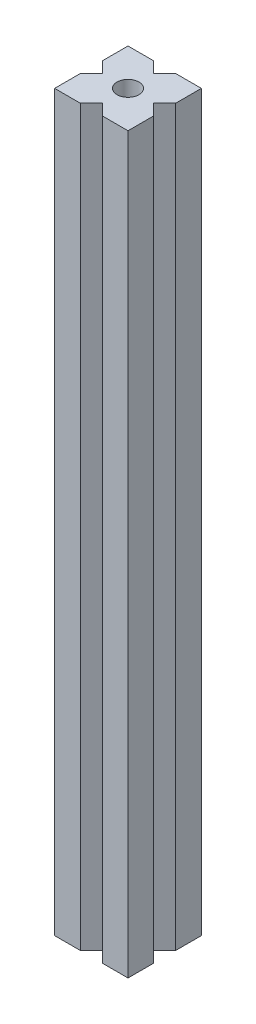
SolidWorks part; units mm, degrees
ref_plane "Front" through (0, 0, 0) normal (0, 0, 1) x (1, 0, 0)
ref_plane "Top" through (0, 0, 0) normal (0, 1, 0) x (1, 0, 0)
ref_plane "Right" through (0, 0, 0) normal (1, 0, 0) x (0, 0, -1)
sketch "Skizze1" plane through (0, 0, 0) normal (0, 1, 0) x (1, 0, 0)
  line L1 (0, 0) -> (20, 0)
  line L2 (0, 0) -> (0, 20)
  line L3 (0, 20) -> (20, 20)
  line L4 (20, 0) -> (20, 20)
  dimension "D1" = 20
extrude "Aufsatz-Linear austragen1" add sketch "Skizze1" along normal blind 200
sketch "Skizze2" plane through (0, 200, 0) normal (0, 1, 0) x (1, 0, 0)
  line L0 (10, 20) -> (10, 0) construction
  line L1 (0, 10) -> (20, 10) construction
  line L2 (7, 20) -> (10, 17)
  line L3 (13, 20) -> (10, 17)
  line L4 (10, 10) -> (20, 20) construction
  line L5 (7, 20) -> (13, 20)
  line L6 (20, 13) -> (17, 10)
  line L7 (20, 7) -> (17, 10)
  line L8 (20, 7) -> (20, 13)
  line L9 (0, 7) -> (0, 13)
  line L10 (0, 7) -> (3, 10)
  line L11 (0, 13) -> (3, 10)
  line L12 (7, 0) -> (13, 0)
  line L13 (13, 0) -> (10, 3)
  line L14 (7, 0) -> (10, 3)
  line L15 (20, 20) -> (0, 20) construction
  line L16 (20, 0) -> (20, 20) construction
  line L17 (0, 0) -> (20, 0) construction
  dimension "D1" = 3
  dimension "D2" = 3
extrude "Schnitt-Linear austragen1" cut sketch "Skizze2" against normal through all
ref_plane "Ebene1" through (10, 0, 0) normal (1, 0, 0) x (0, 0, -1)
sketch "Skizze3" plane through (0, 200, 0) normal (0, 1, 0) x (1, 0, 0)
  line L0 (3, 10) -> (17, 10) construction
  circle A0 centre (10, 10) radius 3
  dimension "D1" = 6
extrude "Schnitt-Linear austragen2" cut sketch "Skizze3" against normal through all
ref_plane "Plane1" through (0, 100, 0) normal (0, 1, 0) x (1, 0, 0)
